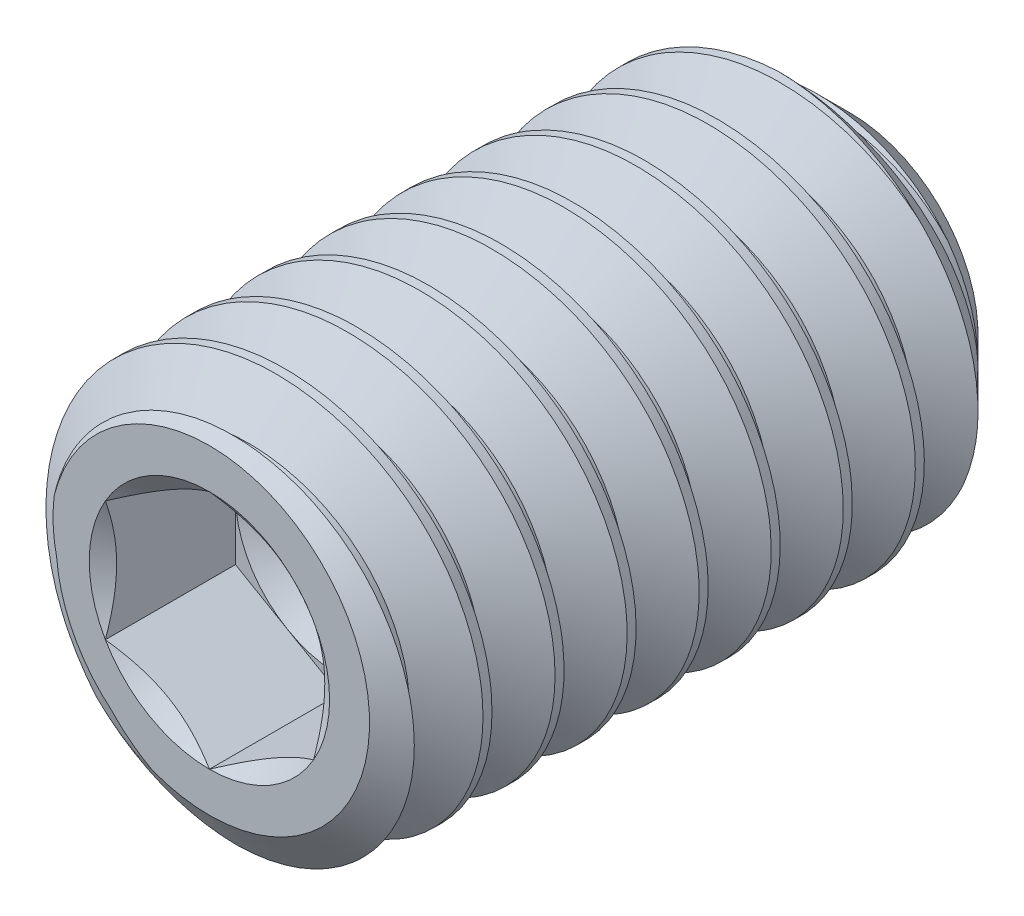
SolidWorks part; units mm, degrees
ref_plane "Front" through (0, 0, 0) normal (0, 0, 1) x (1, 0, 0)
ref_plane "Top" through (0, 0, 0) normal (0, 1, 0) x (1, 0, 0)
ref_plane "Right" through (0, 0, 0) normal (1, 0, 0) x (0, 0, -1)
sketch "Sketch22" plane through (0, 0, 0) normal (1, 0, 0) x (0, 0, -1)
  line L0 (-2, 0) -> (-2, 1)
  line L1 (-2, 1) -> (-1.8249, 1.25)
  line L2 (-1.8249, 1.25) -> (1.55, 1.25)
  line L3 (1.55, 1.25) -> (2, 0.8)
  line L4 (-0.1375, 1.25) -> (-0.1375, -1.25) construction
  line L5 (2, 0) -> (-2, 0)
  line L6 (-2, 1) -> (-2, -1) construction
  line L7 (2, 0) -> (2, 0.8)
  point P11 (-0.1375, 0)
  dimension "Length" = 4
  dimension "D3" = 35
  dimension "D6" = 45
  dimension "Dia" = 2.5
  dimension "D1" = 2
  dimension "D2" = 0.45
revolve "Revolve1" add sketch "Sketch22" angle 360 about L5
ref_plane "Plane1" through (0, 0, -2) normal (0, 0, 1) x (1, 0, 0)
sketch "Sketch27" plane through (0, 0, -2) normal (0, 0, 1) x (1, 0, 0)
  circle A0 centre (0, 0) radius 1.25 construction
  circle A1 centre (0, 0) radius 1.25
curve "Helix/Spiral1" pitch 0.45 height 4.45 radius 1.25 centre (0, 0, -2) axis (0, 0, 1) start towards (0, 1, 0)
sketch "Sketch28" plane through (0, 0, 0) normal (1, 0, 0) x (0, 0, -1)
  line L0 (2, 1.25) -> (2.3938, 1.25)
  line L1 (2.3938, 1.25) -> (2.225, 0.9577)
  line L2 (2.225, 0.9577) -> (2.1688, 0.9577)
  line L3 (2.1688, 0.9577) -> (2, 1.25)
  line L4 (2.0844, 1.1039) -> (2.3094, 1.1039) construction
  line L6 (-1.8249, 1.25) -> (1.55, 1.25) construction
  dimension "D1" = 0.0563
  dimension "D3" = 60
  dimension "D2" = 0.225
sweep "Cut-Sweep2" cut profiles "Sketch28" path "Helix/Spiral1" align with end faces yes
sketch "Sketch23" plane through (0, 0, 2) normal (0, 0, 1) x (1, 0, 0)
  line L1 (0, 0.7506) -> (-0.65, 0.3753)
  line L2 (-0.65, 0.3753) -> (-0.65, -0.3753)
  line L3 (-0.65, -0.3753) -> (0, -0.7506)
  line L4 (0, -0.7506) -> (0.65, -0.3753)
  line L5 (0.65, -0.3753) -> (0.65, 0.3753)
  line L6 (0.65, 0.3753) -> (0, 0.7506)
  circle A0 centre (0, 0) radius 0.65 construction
  dimension "Hex" = 1.3
extrude "Cut-Extrude10" cut sketch "Sketch23" against normal blind 0.8125
sketch "Sketch24" plane through (0, 0, 2) normal (0, 0, 1) x (1, 0, 0)
  circle A0 centre (0, 0) radius 0.7506
extrude "Cut-Extrude11" cut sketch "Sketch24" against normal through all draft 55
sketch "Sketch26" plane through (0, 0, 1.1875) normal (0, 0, 1) x (1, 0, 0)
  circle A0 centre (0, 0) radius 0.65 construction
  circle A1 centre (0, 0) radius 0.65
extrude "Cut-Extrude12" cut sketch "Sketch26" against normal through all draft 60
sketch "Sketch30" plane through (0, 0, 0) normal (1, 0, 0) x (0, 0, -1)
  line L0 (-1.8249, 1.25) -> (1.55, 1.25) construction
  line L1 (-2, 0) -> (-2, 1) construction
  line L2 (2, 0) -> (2, 0.8) construction
  point P0 (-2, 1.25)
  point P1 (2, 1.25)
  point P2 (2, -1.25)
  point P11 (0.875, -1.25)
  dimension "D1" = 1.125
equation "\"D1@Sketch28\" = \"D4@Helix/Spiral1\" * .125"
equation "\"D2@Sketch28\" = \"D4@Helix/Spiral1\" * .5"
equation "\"D3@Helix/Spiral1\" = \"Length@Sketch22\" + \"D4@Helix/Spiral1\""
equation "\"D1@Sketch30\" = \"D4@Helix/Spiral1\" * 2.5"
equation "\"hex Depth@Cut-Extrude10\" = \"Hex@Sketch23\" * .625"
equation "\"D1@Sketch22\" = \"Dia@Sketch22\" * .8"
equation "\"D2@Sketch22\" = \"D4@Helix/Spiral1\""
